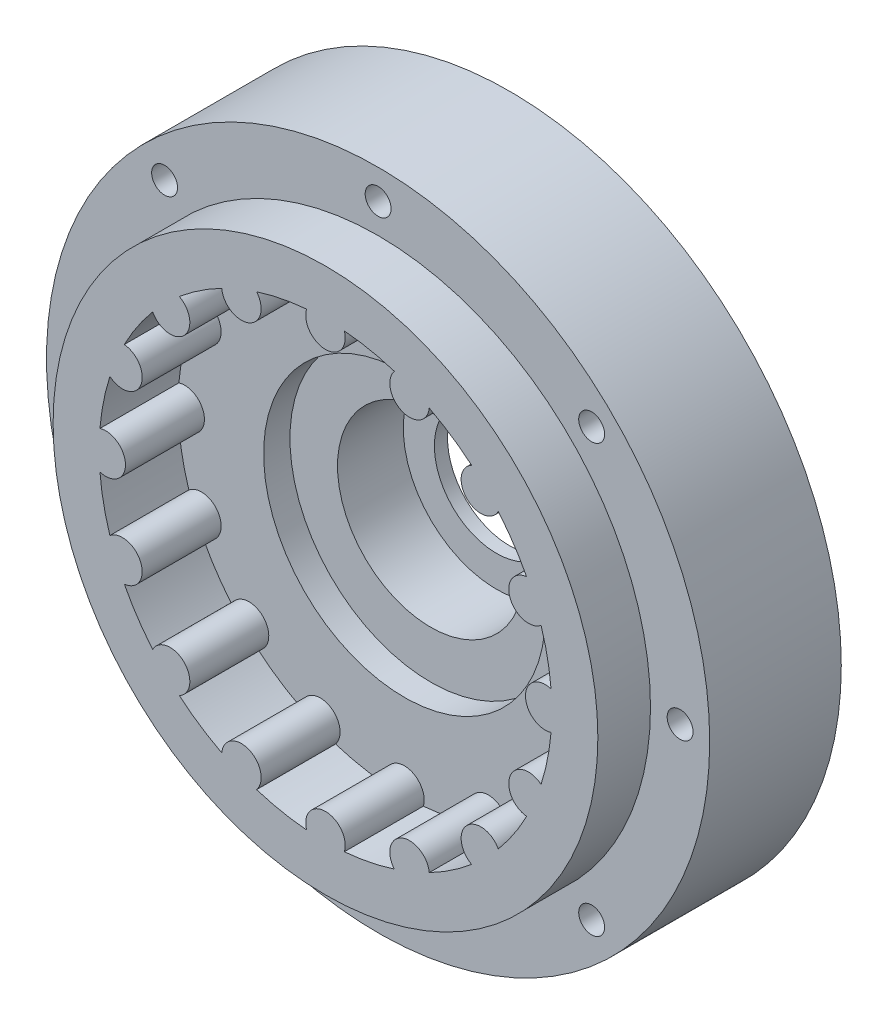
SolidWorks part; units mm, degrees
material "ABS"
ref_plane "Front Plane" through (0, 0, 0) normal (0, 0, 1) x (1, 0, 0)
ref_plane "Top Plane" through (0, 0, 0) normal (0, 1, 0) x (1, 0, 0)
ref_plane "Right Plane" through (0, 0, 0) normal (1, 0, 0) x (0, 0, -1)
sketch "Sketch1" plane through (0, 0, 0) normal (0, 0, 1) x (1, 0, 0)
  circle A0 centre (0, 0) radius 32.004
  dimension "D1" = 64.008
extrude "Boss-Extrude1" add sketch "Sketch1" along normal blind 12.7
sketch "Sketch2" plane through (0, 0, 12.7) normal (0, 0, 1) x (1, 0, 0)
  circle A0 centre (0, 0) radius 26.289
  circle A1 centre (0, 0) radius 32.004
  circle A2 centre (0, 0) radius 32.004
  dimension "D1" = 0
  dimension "D2" = 5.715
extrude "Cut-Extrude1" cut sketch "Sketch2" against normal blind 2.54 flip side to cut
sketch "Sketch3" plane through (0, 0, 10.16) normal (0, 0, 1) x (1, 0, 0)
  line L0 (0, 0) -> (0, 21.209) construction
  circle A1 centre (0, 21.209) radius 1.905
  circle A3 centre (0, 0) radius 21.209 construction
  circle A13 centre (8.1163, 19.5946) radius 1.905
  circle A14 centre (14.997, 14.997) radius 1.905
  circle A15 centre (19.5946, 8.1163) radius 1.905
  circle A16 centre (21.209, 0) radius 1.905
  circle A17 centre (19.5946, -8.1163) radius 1.905
  circle A18 centre (14.997, -14.997) radius 1.905
  circle A19 centre (8.1163, -19.5946) radius 1.905
  circle A20 centre (0, -21.209) radius 1.905
  circle A21 centre (-8.1163, -19.5946) radius 1.905
  circle A22 centre (-14.997, -14.997) radius 1.905
  circle A23 centre (-19.5946, -8.1163) radius 1.905
  circle A24 centre (-21.209, 0) radius 1.905
  circle A25 centre (-19.5946, 8.1163) radius 1.905
  circle A26 centre (-14.997, 14.997) radius 1.905
  circle A27 centre (-8.1163, 19.5946) radius 1.905
  dimension "D2" = 3.81
  dimension "D3" = 16
  dimension "D1" = 42.418
  dimension "D4" = 21.209
sketch "Sketch4" plane through (0, 0, 10.16) normal (0, 0, 1) x (1, 0, 0)
  circle A39 centre (0, 0) radius 27.559 construction
  circle A40 centre (0, 0) radius 13.589
  circle A41 centre (0, 0) radius 26.289 construction
  dimension "D2" = 55.118
  dimension "D1" = 13.97
extrude "Cut-Extrude3" cut sketch "Sketch4" against normal blind 2.54 contours A40 region at (0, 0, 10.16)
sketch "Sketch5" plane through (0, 0, 7.62) normal (0, 0, 1) x (1, 0, 0)
  circle A0 centre (0, 0) radius 9
  circle A1 centre (0, 0) radius 6
  dimension "D1" = 18
  dimension "D2" = 12
extrude "Cut-Extrude4" cut sketch "Sketch5" against normal through all contours A1 region at (0, 0, 7.62)
sketch "Sketch6" plane through (0, 0, 12.7) normal (0, 0, 1) x (1, 0, 0)
  line L0 (0, 0) -> (0, 32.004) construction
  line L1 (0, 0) -> (22.6302, 22.6302) construction
  line L2 (0, 0) -> (32.004, 0) construction
  line L3 (0, 0) -> (22.6302, -22.6302) construction
  line L4 (0, 0) -> (0, -32.004) construction
  line L5 (0, 0) -> (-22.6302, -22.6302) construction
  line L6 (0, 0) -> (-32.004, 0) construction
  line L7 (0, 0) -> (-22.6302, 22.6302) construction
  line L8 (0, 0) -> (0, 29.1465) construction
  circle A0 centre (0, 0) radius 32.004 construction
  point P6 (0, 29.1465)
  point P16 (20.6097, 20.6097)
  point P18 (29.1465, 0)
  point P20 (20.6097, -20.6097)
  point P22 (0, -29.1465)
  point P24 (-20.6097, -20.6097)
  point P26 (-29.1465, 0)
  point P28 (-20.6097, 20.6097)
  dimension "D1" = 29.1465
  dimension "D2" = 8
hole_wizard "M3x0.5 Tapped Hole1" positions "Sketch6" profile "Sketch7" tap size "M3x0.5" standard "ANSI Metric" end condition through all
sketch "Sketch7" plane through (-20.6097, 20.6097, 12.7) normal (1, 0, 0) x (0, -1, 0)
  line L0 (0, 0) -> (0, 12.7)
  line L1 (0, 12.7) -> (1.25, 12.7)
  line L2 (1.25, 12.7) -> (1.25, 0)
  line L5 (1.25, 0) -> (0, 0)
  line L11 (0, -6.35) -> (0, 107.95) construction
  dimension "Thru Tap Drill Dia." = 2.5
  dimension "Thru Tap Drill Depth" = 12.7
cosmetic thread "Hole Thread1" parameters "D2"=3
cosmetic thread "Hole Thread2" parameters "D2"=3
cosmetic thread "Hole Thread3" parameters "D2"=3
cosmetic thread "Hole Thread4" parameters "D2"=3
cosmetic thread "Hole Thread5" parameters "D2"=3
cosmetic thread "Hole Thread6" parameters "D2"=3
cosmetic thread "Hole Thread7" parameters "D2"=3
cosmetic thread "Hole Thread8" parameters "D2"=3
extrude "Cut-Extrude5" cut sketch "Sketch5<3>" against normal blind 6.35
sketch "Sketch5<3>" plane through (0, 0, 7.62) normal (0, 0, 1) x (1, 0, 0) same geometry as "Sketch5"
sketch "Sketch8" plane through (0, 0, 10.16) normal (0, 0, 1) x (1, 0, 0)
  circle A0 centre (0, 0) radius 21.844
  circle A1 centre (0, 0) radius 26.289
  circle A2 centre (0, 0) radius 26.289
  dimension "D1" = 0
  dimension "D2" = 4.445
extrude "Boss-Extrude2" add sketch "Sketch8" along normal blind 7.62
extrude "Boss-Extrude3" add sketch "Sketch3" along normal blind 7.62
